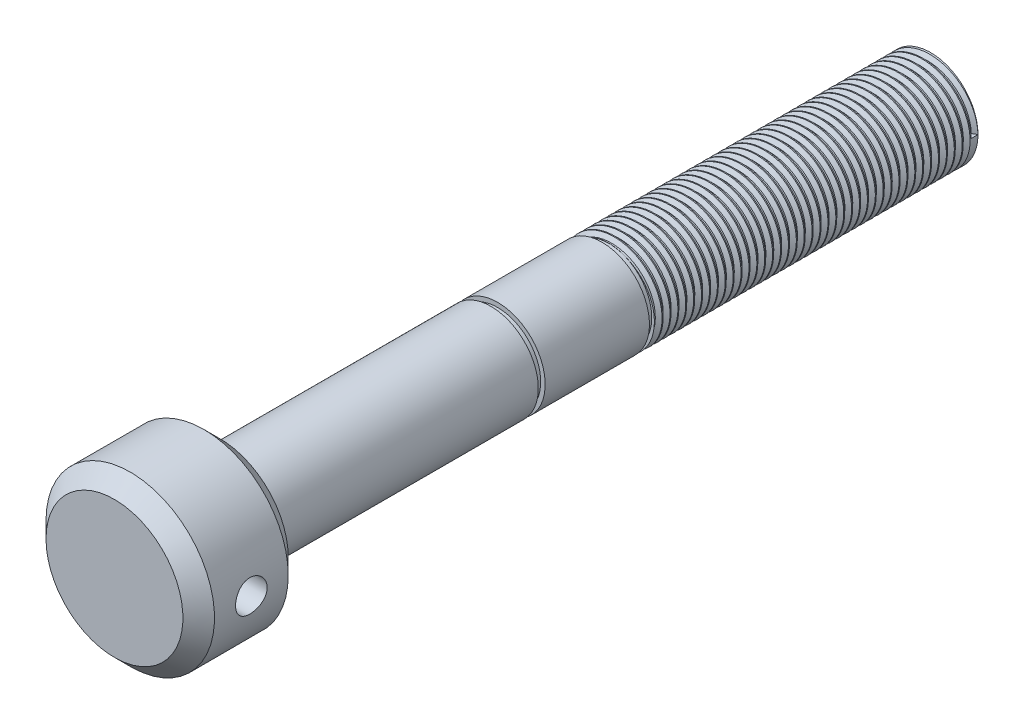
SolidWorks part; units mm, degrees
ref_plane "Front Plane" through (0, 0, 0) normal (0, 0, 1) x (1, 0, 0)
ref_plane "Top Plane" through (0, 0, 0) normal (0, 1, 0) x (1, 0, 0)
ref_plane "Right Plane" through (0, 0, 0) normal (1, 0, 0) x (0, 0, -1)
sketch "Sketch1" plane through (0, 0, 0) normal (0, 0, 1) x (1, 0, 0)
  circle A0 centre (0, 0) radius 16
  dimension "D1" = 32
extrude "Boss-Extrude1" add sketch "Sketch1" along normal blind 20
chamfer "Chamfer1" distance 3 angle 45 2 edges at (16, 0, 0) (16, 0, 20)
sketch "Sketch2" plane through (0, 0, 0) normal (0, 0, -1) x (-1, 0, 0)
  circle A0 centre (0, 0) radius 9
  dimension "D1" = 18
extrude "Boss-Extrude2" add sketch "Sketch2" along normal blind 135
sketch "Sketch3" plane through (0, 0, 0) normal (1, 0, 0) x (0, 0, -1)
  line L0 (135, 9) -> (0, 9) construction
  line L1 (135, 9) -> (0, 9)
  line L2 (-20, 13) -> (-20, -13) construction
  line L3 (52.8, 9) -> (51.5, 9)
  line L4 (52.8, 9) -> (52.8, 8.15)
  line L5 (52.8, 8.15) -> (51.5, 8.15)
  line L6 (51.5, 9) -> (51.5, 8.15)
  line L7 (73.9, 9) -> (73.9, 8.15)
  line L12 (73.9, 8.15) -> (72.6, 8.15)
  line L13 (72.6, 8.15) -> (72.6, 9)
  line L14 (72.6, 9) -> (73.9, 9)
  line L15 (73.9, 9) -> (72.6, 9)
  line L16 (135, 0) -> (-19.9752, 0) construction
  dimension "D1" = 71.5
  dimension "D2" = 1.3
  dimension "D3" = 0.85
  dimension "D4" = 22.4
  dimension "D5" = 1.3
  dimension "D6" = 0.85
revolve "Cut-Revolve1" cut sketch "Sketch3" angle 360 about L16 region at (0, 8.575, -73.25) region at (0, 8.575, -52.15)
sketch "Sketch4" plane through (0, 0, 0) normal (1, 0, 0) x (0, 0, -1)
  line L0 (0, 0) -> (-20, 0)
  line L1 (-20, 13) -> (-20, -13) construction
  circle A0 centre (-10, 0) radius 3
  dimension "D1" = 6
extrude "Cut-Extrude1" cut sketch "Sketch4" along normal through all both and the other way through all contours L0 A0 | L0 A0 region at (0, -1.2732, 10) region at (0, 1.2732, 10)
thread "Thread1" pitch 1.5 method cut profile "Thread Profile1" start angle 0, offset 0, length 0, pitch 1.5, diameter 18
ref_plane "Plane1" through (9, 0, -135) normal (0, -1, 0) x (1, 0, 0)
sketch "Thread Profile1" plane through (9, 0, -135) normal (0, -1, 0) x (1, 0, 0)
  line L0 (0, 0) -> (0, 1.5) construction
  line L11 (0, 0) -> (0, 1.3125)
  line L12 (0, 1.3125) -> (-0.8119, 0.8437)
  line L13 (-0.8119, 0.8437) -> (-0.8119, 0.4687)
  line L15 (-0.8119, 0.4687) -> (0, 0)
  line L17 (-0.8119, 0.6562) -> (0, 0.6562) construction
  point P2 (0, 0)
  dimension "Pitch" = 1.5
  dimension "Profile_Angle" = 60
  dimension "Profile_Land" = 0.375
  dimension "Profile_Height" = 0.8119
